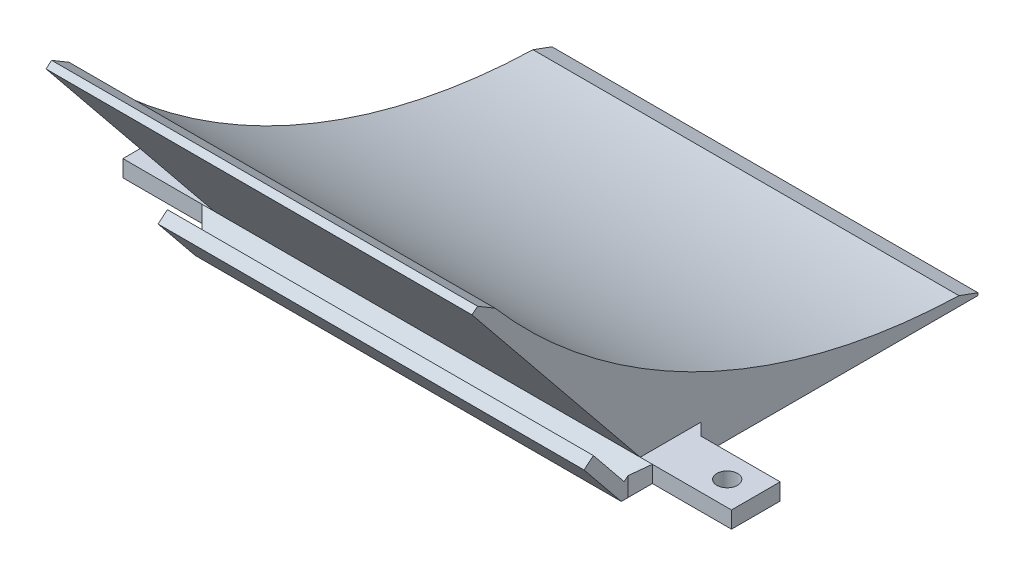
SolidWorks part; units mm, degrees
ref_plane "Front Plane" through (0, 0, 0) normal (0, 0, 1) x (1, 0, 0)
ref_plane "Top Plane" through (0, 0, 0) normal (0, 1, 0) x (1, 0, 0)
ref_plane "Right Plane" through (0, 0, 0) normal (1, 0, 0) x (0, 0, -1)
sketch "Sketch2" plane through (93.0034, 0, 0) normal (-1, 0, 0) x (0, 0, 1)
  line L0 (0, 0) -> (206.9217, 0) construction
  line L1 (210.0714, 3.884) -> (206.9217, 0) construction
  line L2 (207.7413, 5.7736) -> (203.0593, 0) construction
  line L3 (210.0714, 3.884) -> (229.5972, 27.9619) construction
  line L4 (207.7413, 5.7736) -> (227.2671, 29.8515) construction
  line L5 (207.46, 5.7442) -> (210.1008, 3.6027)
  line L6 (151.9511, 2.5) -> (204.8291, 2.5) construction
  line L7 (210.0714, 3.884) -> (207.7413, 5.7736) construction
  line L8 (208.9064, 4.8288) -> (208.7804, 4.6735) construction
  line L9 (210.1008, 3.6027) -> (215.1397, 9.8164)
  line L10 (207.46, 5.7442) -> (235.095, 39.822)
  line L11 (215.1397, 9.8164) -> (216.6931, 8.5566)
  line L12 (216.6931, 8.5566) -> (210.5651, 1)
  line L13 (210.5651, 1) -> (151.9511, 1)
  line L14 (235.095, 39.822) -> (233.3086, 41.2707)
  line L18 (151.9511, 1) -> (151.9511, 2.5)
  line L19 (210.0714, 3.884) -> (229.5972, 27.9619) construction
  line L20 (207.7413, 5.7736) -> (227.2671, 29.8515) construction
  line L21 (210.0714, 3.884) -> (207.7413, 5.7736) construction
  line L26 (186.7375, 34.25) -> (184.1069, 39.7702) construction
  line L27 (203.0593, 0) -> (186.7375, 34.25) construction
  arc A0 (233.3086, 41.2707) -> (151.9511, 2.5) centre (151.9511, 107.2468) cw
  point P11 (208.7804, 4.6735)
  point P21 (0, 0)
  point P27 (197.0128, 12.6881)
  dimension "D6" = 1.5
  dimension "D7" = 8
  dimension "D1" = 0.2
  dimension "D2" = 0.2
  dimension "D3" = 2
  dimension "D4" = 1
  dimension "D5" = 30
  dimension "D11" = 6.115
extrude "Boss-Extrude1" add sketch "Sketch2" against normal up to surface (70 mm away) contours L14 A0 L18 L13 L12 L11 L9 L5 L10 region at (93.0034, 11.0697, 200.16)
chamfer "Chamfer1" distance 1.1 distance2 3 1 edges at (128.0034, 2.5, 151.9511) first distance on face at (128.0034, 1.75, 151.9511)
chamfer "Chamfer2" distance 3 distance2 1.1 1 edges at (128.0034, 41.2707, 233.3086) first distance on face at (128.0034, 17.6401, 196.3065)
sketch "Sketch3" plane through (93.0034, 0, 0) normal (-1, 0, 0) x (0, 0, 1)
  line L0 (210.5651, 1) -> (151.9511, 1) construction
  line L1 (207.46, 5.7442) -> (199.46, 5.7442)
  line L2 (207.46, 5.7442) -> (207.46, 3)
  line L3 (207.46, 3) -> (199.46, 3)
  line L4 (199.46, 5.7442) -> (199.46, 3)
  dimension "D1" = 2
  dimension "D2" = 8
extrude "Boss-Extrude2" add sketch "Sketch3" along normal blind 15
hole_wizard "M3 Clearance Hole1" positions "Sketch6" profile "Sketch5" hole size "M3" standard "ANSI Metric" end condition through all
sketch "Sketch6" plane through (0, 5.7442, 0) normal (0, 1, 0) x (1, 0, 0)
  line L0 (78.0034, -203.46) -> (82.7034, -203.46) construction
  line L1 (78.0034, -207.46) -> (78.0034, -199.46) construction
  point P2 (82.7034, -203.46)
  point P10 (82.7034, -203.46)
  dimension "D1" = 4.7
sketch "Sketch5" plane through (82.7034, 5.7442, 203.46) normal (1, 0, 0) x (0, 0, 1)
  line L0 (0, 0) -> (0, 4.7442)
  line L1 (0, 4.7442) -> (1.7, 4.7442)
  line L2 (1.7, 4.7442) -> (1.7, 0)
  line L5 (1.7, 0) -> (0, 0)
  line L11 (0, -6.35) -> (0, 107.95) construction
  dimension "Thru Hole Dia." = 3.4
  dimension "Thru Hole Depth" = 4.7442
ref_plane "Bisection" through (128.0034, 0, 0) normal (1, 0, 0) x (0, 0, -1)
mirror "Mirror1" about plane through (128.0034, 0, 0) normal (1, 0, 0) of "Boss-Extrude2", "M3 Clearance Hole1"
chamfer "Chamfer3" distance 2 angle 45 6 edges at (163.0034, 4.3721, 207.46) (163.0034, 4.3721, 199.46) (163.0034, 3, 203.46) (93.0034, 4.3721, 199.46) (93.0034, 4.3721, 207.46) (93.0034, 3, 203.46)
